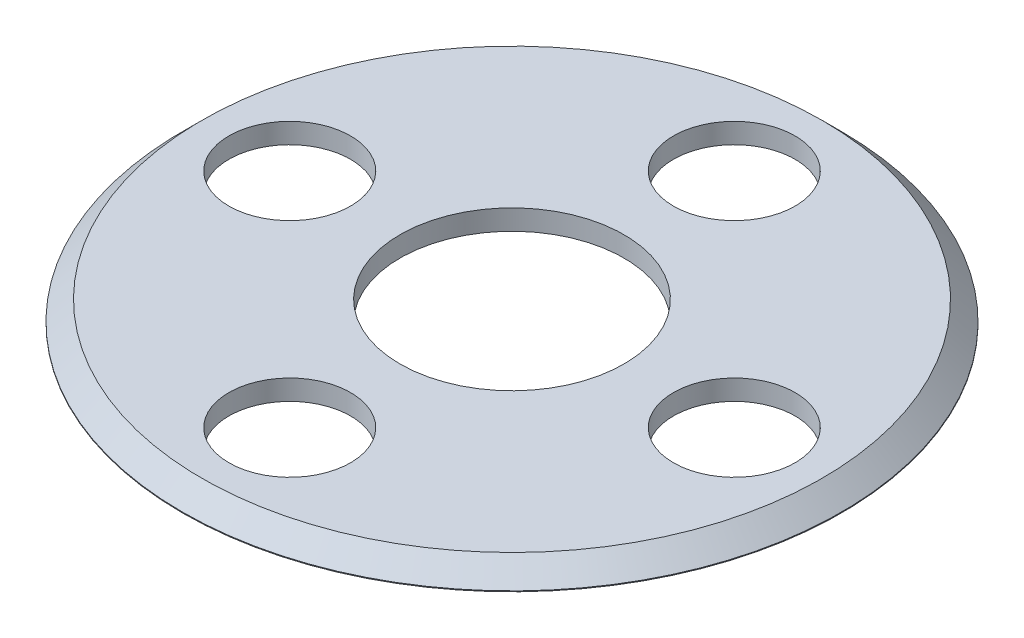
SolidWorks part; units mm, degrees
other "DetailItem2"
other "DetailItem3"
other "DetailItem4"
material "Alum Plate"
ref_plane "Front Plane" through (0, 0, 0) normal (0, 0, 1) x (1, 0, 0)
ref_plane "Top Plane" through (0, 0, 0) normal (0, 1, 0) x (1, 0, 0)
ref_plane "Right Plane" through (0, 0, 0) normal (1, 0, 0) x (0, 0, -1)
ref_axis "Centerline" through (0, 10.4775, 0) along (0, -1, 0)
sketch "Sketch1" plane through (0, 0, 0) normal (0, 1, 0) x (1, 0, 0)
  circle A0 centre (0, 0) radius 23.9697
  dimension "OuterDiameter" = 47.9394
extrude "ToothOD" add sketch "Sketch1" along normal mid plane 4.7625
sketch "Sketch2" plane through (0, 2.3813, 0) normal (0, 1, 0) x (1, 0, 0)
  line L0 (0, 22.8013) -> (50000, 22.8013) construction
  line L1 (0, 23.9697) -> (50000, 23.9697) construction
  line L2 (0, 0) -> (0, 50000) construction
  arc A0 (-0.937, 23.5198) -> (0, 22.8013) centre (0, 23.7716) ccw
  arc A1 (-1.1386, 23.9426) -> (1.1386, 23.9426) centre (0, 0) cw
  circle A2 centre (0, 0) radius 23.9697 construction
  arc A3 (-0.937, 23.5198) -> (-1.0078, 23.7716) centre (-11.9754, 20.5533) ccw
  arc A4 (-1.0078, 23.7716) -> (-1.1386, 23.9426) centre (-1.2954, 23.6872) ccw
  circle A5 centre (0, 0) radius 23.9697 construction
  arc A6 (0.937, 23.5198) -> (1.0078, 23.7716) centre (11.9754, 20.5533) cw
  arc A7 (1.0078, 23.7716) -> (1.1386, 23.9426) centre (1.2954, 23.6872) cw
  arc A8 (0, 22.8013) -> (0.937, 23.5198) centre (0, 23.7716) ccw
  dimension "D1" = 1.9406
  dimension "D3" = 22.86
  dimension "D4" = 0.5994
  dimension "D2" = 1.1684
  dimension "D5" = 1.2954
extrude "ToothProfile" cut sketch "Sketch2" against normal through all
pattern_circular "ToothPattern" count 51 over 360 about axis through (0, 2.3813, 0) along (0, -1, 0) of "ToothProfile"
sketch "Sketch4" plane through (0, 0, 0) normal (0, 0, 1) x (1, 0, 0)
  line L0 (0, -5.08) -> (24.2237, -5.08)
  line L1 (0, -6.35) -> (25.7477, -6.35)
  line L2 (0, -6.35) -> (0, -5.08)
  line L3 (25.7477, -6.35) -> (25.7477, -5.842)
  line L4 (0, 0) -> (50000, 0) construction
  line L5 (25.7477, 6.35) -> (25.7477, 5.842)
  line L6 (0, 6.35) -> (0, 5.08)
  line L7 (0, 6.35) -> (25.7477, 6.35)
  line L8 (0, 5.08) -> (24.2237, 5.08)
  arc A0 (24.2237, -5.08) -> (24.6788, -5.1726) centre (23.944, -7.618) cw
  arc A2 (24.6788, -5.1726) -> (25.7477, -5.842) centre (23.5462, -8.1694) cw
  arc A3 (24.6788, 5.1726) -> (25.7477, 5.842) centre (23.5462, 8.1694) ccw
  arc A4 (24.2237, 5.08) -> (24.6788, 5.1726) centre (23.944, 7.618) ccw
  dimension "FlangeID" = 24.2237
  dimension "FlangeOD" = 25.7477
  dimension "D1" = 1.27
  dimension "D2" = 0.508
  dimension "D3" = 5.08
  dimension "D4" = 12.7
sketch "Sketch7" plane through (0, 0, 0) normal (0, -1, 0) x (1, 0, 0)
  line L1 (3.6662, 6.35) -> (-3.6662, 6.35)
  line L2 (-3.6662, 6.35) -> (-7.3323, 0)
  line L3 (-7.3323, 0) -> (-3.6662, -6.35)
  line L4 (-3.6662, -6.35) -> (3.6662, -6.35)
  line L5 (3.6662, -6.35) -> (7.3323, 0)
  line L6 (7.3323, 0) -> (3.6662, 6.35)
  circle A0 centre (0, 0) radius 6.35 construction
  dimension "HexBoreDi," = 12.7
extrude "Bore" [suppressed] cut sketch "Sketch7" against normal through all both and the other way through all
sketch "Sketch13" plane through (0, 2.3813, 0) normal (0, 1, 0) x (1, 0, 0)
  line L0 (-3.81, 20.2565) -> (3.81, 20.2565) construction
  line L4 (0, 20.2565) -> (0, 17.399) construction
  arc A0 (-3.81, 20.2565) -> (3.81, 20.2565) centre (0, 17.399) ccw
  circle A1 centre (0, 0) radius 8.7694
  arc A2 (3.81, 20.2565) -> (-3.81, 20.2565) centre (0, 17.399) ccw
  dimension "D1" = 9.525
  dimension "D3" = 17.5387
  dimension "D2" = 17.399
  dimension "D4" = 7.62
extrude "Cut-Extrude2" cut sketch "Sketch13" against normal through all
pattern_circular "CirPattern1" count 4 over 360 about axis through (0, -2.3813, 0) along (0, 1, 0) of "Cut-Extrude2"
sketch "Sketch14" plane through (0, 2.3813, 0) normal (0, 1, 0) x (1, 0, 0)
  circle A0 centre (0, 0) radius 22.733
  circle A1 centre (0, 0) radius 23.9697
  arc A3 (-3.2802, -23.7442) -> (-2.6104, -23.8271) centre (0, 0) ccw construction
  dimension "D1" = 45.466
extrude "Cut-Extrude3" [suppressed] cut sketch "Sketch14" against normal through all
sketch "Sketch15" plane through (0, 2.3813, 0) normal (0, 1, 0) x (1, 0, 0)
  circle A0 centre (0, 0) radius 25.7969
  arc A306 (6.9442, 22.9418) -> (6.7756, 22.8078) centre (7.0339, 22.6558) ccw
  arc A307 (6.7756, 22.8078) -> (6.6455, 22.5808) centre (16.6269, 17.0116) ccw
  arc A308 (4.8281, 23.038) -> (6.6455, 22.5808) centre (5.7982, 23.0536) ccw
  arc A309 (4.8281, 23.038) -> (4.8208, 23.2994) centre (-6.6004, 22.8535) ccw
  arc A310 (4.8208, 23.2994) -> (4.7357, 23.4972) centre (4.5214, 23.2877) ccw
  arc A311 (4.7357, 23.4972) -> (4.0723, 23.6213) centre (0, 0) ccw
  arc A312 (4.0723, 23.6213) -> (3.9214, 23.4676) centre (4.1965, 23.3485) ccw
  arc A313 (3.9214, 23.4676) -> (3.8202, 23.2264) centre (14.4104, 18.9259) ccw
  arc A314 (1.9604, 23.4567) -> (3.8202, 23.2264) centre (2.9212, 23.5914) ccw
  arc A315 (1.9604, 23.4567) -> (1.9211, 23.7153) centre (-9.3589, 21.8692) ccw
  arc A316 (1.9211, 23.7153) -> (1.8123, 23.9011) centre (1.6253, 23.6668) ccw
  arc A317 (1.8123, 23.9011) -> (1.1386, 23.9426) centre (0, 0) ccw
  arc A318 (1.1386, 23.9426) -> (1.0078, 23.7716) centre (1.2954, 23.6872) ccw
  arc A319 (1.0078, 23.7716) -> (0.937, 23.5198) centre (11.9754, 20.5533) ccw
  arc A320 (-0.937, 23.5198) -> (0.937, 23.5198) centre (0, 23.7716) ccw
  arc A321 (-0.937, 23.5198) -> (-1.0078, 23.7716) centre (-11.9754, 20.5533) ccw
  arc A322 (-1.0078, 23.7716) -> (-1.1386, 23.9426) centre (-1.2954, 23.6872) ccw
  arc A323 (-1.1386, 23.9426) -> (-1.8123, 23.9011) centre (0, 0) ccw
  arc A324 (-1.8123, 23.9011) -> (-1.9211, 23.7153) centre (-1.6253, 23.6668) ccw
  arc A325 (-1.9211, 23.7153) -> (-1.9604, 23.4567) centre (9.3589, 21.8692) ccw
  arc A326 (-3.8202, 23.2264) -> (-1.9604, 23.4567) centre (-2.9212, 23.5914) ccw
  arc A327 (-3.8202, 23.2264) -> (-3.9214, 23.4676) centre (-14.4104, 18.9259) ccw
  arc A328 (-3.9214, 23.4676) -> (-4.0723, 23.6213) centre (-4.1965, 23.3485) ccw
  arc A329 (-4.0723, 23.6213) -> (-4.7357, 23.4972) centre (0, 0) ccw
  arc A330 (-4.7357, 23.4972) -> (-4.8208, 23.2994) centre (-4.5214, 23.2877) ccw
  arc A331 (-4.8208, 23.2994) -> (-4.8281, 23.038) centre (6.6004, 22.8535) ccw
  arc A332 (-6.6455, 22.5808) -> (-4.8281, 23.038) centre (-5.7982, 23.0536) ccw
  arc A333 (-6.6455, 22.5808) -> (-6.7756, 22.8078) centre (-16.6269, 17.0116) ccw
  arc A334 (-6.7756, 22.8078) -> (-6.9442, 22.9418) centre (-7.0339, 22.6558) ccw
  arc A335 (-6.9442, 22.9418) -> (-7.5873, 22.7372) centre (0, 0) ccw
  arc A336 (-7.5873, 22.7372) -> (-7.6475, 22.5304) centre (-7.3489, 22.5556) ccw
  arc A337 (-7.6475, 22.5304) -> (-7.6226, 22.27) centre (3.742, 23.4914) ccw
  arc A338 (-9.3701, 21.593) -> (-7.6226, 22.27) centre (-8.5873, 22.1663) ccw
  arc A339 (-9.3701, 21.593) -> (-9.527, 21.8023) centre (-18.5914, 14.8394) ccw
  arc A340 (-9.527, 21.8023) -> (-9.7108, 21.9145) centre (-9.7647, 21.6197) ccw
  arc A341 (-9.7108, 21.9145) -> (-10.324, 21.6324) centre (0, 0) ccw
  arc A342 (-10.324, 21.6324) -> (-10.3583, 21.4198) centre (-10.065, 21.4816) ccw
  arc A343 (-10.3583, 21.4198) -> (-10.3015, 21.1645) centre (0.8268, 23.7732) ccw
  arc A344 (-11.9526, 20.2779) -> (-10.3015, 21.1645) centre (-11.2462, 20.9431) ccw
  arc A345 (-11.9526, 20.2779) -> (-12.1341, 20.4663) centre (-20.2741, 12.4423) ccw
  arc A346 (-12.1341, 20.4663) -> (-12.3303, 20.5551) centre (-12.3475, 20.2559) ccw
  arc A347 (-12.3303, 20.5551) -> (-12.9041, 20.1998) centre (0, 0) ccw
  arc A348 (-12.9041, 20.1998) -> (-12.912, 19.9846) centre (-12.6285, 20.0819) ccw
  arc A349 (-12.912, 19.9846) -> (-12.8243, 19.7382) centre (-2.1009, 23.6946) ccw
  arc A350 (-14.3539, 18.6554) -> (-12.8243, 19.7382) centre (-13.7346, 19.4023) ccw
  arc A351 (-14.3539, 18.6554) -> (-14.5572, 18.82) centre (-21.6494, 9.8565) ccw
  arc A352 (-14.5572, 18.82) -> (-14.7628, 18.884) centre (-14.7431, 18.585) ccw
  arc A353 (-14.7628, 18.884) -> (-15.2886, 18.4609) centre (0, 0) ccw
  arc A354 (-15.2886, 18.4609) -> (-15.27, 18.2464) centre (-15.0006, 18.3778) ccw
  arc A355 (-15.27, 18.2464) -> (-15.1527, 18.0126) centre (-4.9968, 23.2569) ccw
  arc A356 (-16.5376, 16.75) -> (-15.1527, 18.0126) centre (-16.0148, 17.5674) ccw
  arc A357 (-16.5376, 16.75) -> (-16.7596, 16.8885) centre (-22.6966, 7.1213) ccw
  arc A358 (-16.7596, 16.8885) -> (-16.9715, 16.9267) centre (-16.9153, 16.6323) ccw
  arc A359 (-16.9715, 16.9267) -> (-17.4414, 16.4422) centre (0, 0) ccw
  arc A360 (-17.4414, 16.4422) -> (-17.3966, 16.2316) centre (-17.1454, 16.3951) ccw
  arc A361 (-17.3966, 16.2316) -> (-17.2514, 16.014) centre (-7.8169, 22.4665) ccw
  arc A362 (-18.4707, 14.5908) -> (-17.2514, 16.014) centre (-18.0523, 15.4662) ccw
  arc A363 (-18.4707, 14.5908) -> (-18.708, 14.7009) centre (-23.3997, 4.2782) ccw
  arc A364 (-18.708, 14.7009) -> (-18.923, 14.7128) centre (-18.831, 14.4276) ccw
  arc A365 (-18.923, 14.7128) -> (-19.3297, 14.1742) centre (0, 0) ccw
  arc A366 (-19.3297, 14.1742) -> (-19.2594, 13.9707) centre (-19.0302, 14.1638) ccw
  arc A367 (-19.2594, 13.9707) -> (-19.0886, 13.7726) centre (-10.5185, 21.3356) ccw
  arc A368 (-20.1237, 12.2104) -> (-19.0886, 13.7726) centre (-19.8161, 13.1306) ccw
  arc A369 (-20.1237, 12.2104) -> (-20.3727, 12.2905) centre (-23.7481, 1.3702) ccw
  arc A370 (-20.3727, 12.2905) -> (-20.5876, 12.2759) centre (-20.4612, 12.0041) ccw
  arc A371 (-20.5876, 12.2759) -> (-20.925, 11.6914) centre (0, 0) ccw
  arc A372 (-20.925, 11.6914) -> (-20.8302, 11.4981) centre (-20.6265, 11.7179) ccw
  arc A373 (-20.8302, 11.4981) -> (-20.6364, 11.3225) centre (-13.0607, 19.8813) ccw
  arc A374 (-21.4717, 9.6449) -> (-20.6364, 11.3225) centre (-21.2795, 10.5959) ccw
  arc A375 (-21.4717, 9.6449) -> (-21.7287, 9.6938) centre (-23.7365, -1.5585) ccw
  arc A376 (-21.7287, 9.6938) -> (-21.9401, 9.6529) centre (-21.7813, 9.3987) ccw
  arc A377 (-21.9401, 9.6529) -> (-22.2032, 9.0314) centre (0, 0) ccw
  arc A378 (-22.2032, 9.0314) -> (-22.0853, 8.8511) centre (-21.9102, 9.0943) ccw
  arc A379 (-22.0853, 8.8511) -> (-21.8713, 8.7007) centre (-15.4049, 18.1256) ccw
  arc A380 (-22.4942, 6.9331) -> (-21.8713, 8.7007) centre (-22.4203, 7.9006) ccw
  arc A381 (-22.4942, 6.9331) -> (-22.7552, 6.9501) centre (-23.365, -4.4636) ccw
  arc A382 (-22.7552, 6.9501) -> (-22.96, 6.8836) centre (-22.7712, 6.6508) ccw
  arc A383 (-22.96, 6.8836) -> (-23.1447, 6.2344) centre (0, 0) ccw
  arc A384 (-23.1447, 6.2344) -> (-23.0056, 6.07) centre (-22.8617, 6.3329) ccw
  arc A385 (-23.0056, 6.07) -> (-22.7748, 5.947) centre (-17.5156, 16.0952) ccw
  arc A386 (-23.1757, 4.1163) -> (-22.7748, 5.947) centre (-23.2212, 5.0855) ccw
  arc A387 (-23.1757, 4.1163) -> (-23.4368, 4.1011) centre (-22.6394, -7.3011) ccw
  arc A388 (-23.4368, 4.1011) -> (-23.6319, 4.0099) centre (-23.4159, 3.8021) ccw
  arc A389 (-23.6319, 4.0099) -> (-23.7355, 3.3429) centre (0, 0) ccw
  arc A390 (-23.7355, 3.3429) -> (-23.5772, 3.1969) centre (-23.4666, 3.4755) ccw
  arc A391 (-23.5772, 3.1969) -> (-23.333, 3.1032) centre (-19.3607, 13.8207) ccw
  arc A392 (-23.5059, 1.2371) -> (-23.333, 3.1032) centre (-23.6702, 2.1934) ccw
  arc A393 (-23.5059, 1.2371) -> (-23.7632, 1.1899) centre (-21.5706, -10.0279) ccw
  arc A394 (-23.7632, 1.1899) -> (-23.9456, 1.0754) centre (-23.7057, 0.8957) ccw
  arc A395 (-23.9456, 1.0754) -> (-23.9664, 0.4008) centre (0, 0) ccw
  arc A396 (-23.9664, 0.4008) -> (-23.7913, 0.2753) centre (-23.7159, 0.5653) ccw
  arc A397 (-23.7913, 0.2753) -> (-23.5375, 0.2123) centre (-20.9124, 11.3368) ccw
  arc A398 (-23.4798, -1.6609) -> (-23.5375, 0.2123) centre (-23.7603, -0.732) ccw
  arc A399 (-23.4798, -1.6609) -> (-23.7293, -1.7394) centre (-20.1748, -12.6026) ccw
  arc A400 (-23.7293, -1.7394) -> (-23.8962, -1.8754) centre (-23.6361, -2.0242) ccw
  arc A401 (-23.8962, -1.8754) -> (-23.834, -2.5474) centre (0, 0) ccw
  arc A402 (-23.834, -2.5474) -> (-23.6449, -2.6505) centre (-23.6056, -2.3533) ccw
  arc A403 (-23.6449, -2.6505) -> (-23.3852, -2.6818) centre (-22.147, 8.6809) ccw
  arc A404 (-23.0977, -4.5337) -> (-23.3852, -2.6818) centre (-23.4903, -3.6464) ccw
  arc A405 (-23.0977, -4.5337) -> (-23.3357, -4.6422) centre (-18.4732, -14.9864) ccw
  arc A406 (-23.3357, -4.6422) -> (-23.4846, -4.7978) centre (-23.2082, -4.9135) ccw
  arc A407 (-23.4846, -4.7978) -> (-23.3403, -5.4571) centre (0, 0) ccw
  arc A408 (-23.3403, -5.4571) -> (-23.1399, -5.5361) centre (-23.1375, -5.2364) ccw
  arc A409 (-23.1399, -5.5361) -> (-22.8783, -5.5352) centre (-23.0459, 5.8935) ccw
  arc A410 (-22.3655, -7.3378) -> (-22.8783, -5.5352) centre (-22.8641, -6.5054) ccw
  arc A411 (-22.3655, -7.3378) -> (-22.5883, -7.4747) centre (-16.4915, -17.1429) ccw
  arc A412 (-22.5883, -7.4747) -> (-22.7171, -7.6474) centre (-22.4285, -7.7283) ccw
  arc A413 (-22.7171, -7.6474) -> (-22.4927, -8.2839) centre (0, 0) ccw
  arc A414 (-22.4927, -8.2839) -> (-22.2842, -8.3377) centre (-22.3186, -8.04) ccw
  arc A415 (-22.2842, -8.3377) -> (-22.0247, -8.3048) centre (-23.5955, 3.0168) ccw
  arc A416 (-21.2942, -10.0306) -> (-22.0247, -8.3048) centre (-21.8914, -9.2658) ccw
  arc A417 (-21.2942, -10.0306) -> (-21.4986, -10.1939) centre (-14.2598, -19.0396) ccw
  arc A418 (-21.4986, -10.1939) -> (-21.6051, -10.3811) centre (-21.3087, -10.4259) ccw
  arc A419 (-21.6051, -10.3811) -> (-21.3043, -10.9852) centre (0, 0) ccw
  arc A420 (-21.3043, -10.9852) -> (-21.0907, -11.013) centre (-21.1614, -10.7217) ccw
  arc A421 (-21.0907, -11.013) -> (-20.8372, -10.9484) centre (-23.7874, 0.0943) ccw
  arc A422 (-19.9002, -12.5714) -> (-20.8372, -10.9484) centre (-20.5868, -11.8858) ccw
  arc A423 (-19.9002, -12.5714) -> (-20.0829, -12.7586) centre (-11.812, -20.6476) ccw
  arc A424 (-20.0829, -12.7586) -> (-20.1656, -12.9574) centre (-19.866, -12.9654) ccw
  arc A425 (-20.1656, -12.9574) -> (-19.7928, -13.52) centre (0, 0) ccw
  arc A426 (-19.7928, -13.52) -> (-19.5775, -13.5213) centre (-19.6834, -13.241) ccw
  arc A427 (-19.5775, -13.5213) -> (-19.3339, -13.4261) centre (-23.6187, -2.8296) ccw
  arc A428 (-18.2045, -14.9216) -> (-19.3339, -13.4261) centre (-18.9701, -14.3256) ccw
  arc A429 (-18.2045, -14.9216) -> (-18.3628, -15.1298) centre (-9.1851, -21.9427) ccw
  arc A430 (-18.3628, -15.1298) -> (-18.4205, -15.3373) centre (-18.1221, -15.3085) ccw
  arc A431 (-18.4205, -15.3373) -> (-17.9814, -15.8499) centre (0, 0) ccw
  arc A432 (-17.9814, -15.8499) -> (-17.7675, -15.8247) centre (-17.9071, -15.5595) ccw
  arc A433 (-17.7675, -15.8247) -> (-17.5374, -15.7002) centre (-23.0919, -5.7106) ccw
  arc A434 (-16.2328, -17.0456) -> (-17.5374, -15.7002) centre (-17.0659, -16.5482) ccw
  arc A435 (-16.2328, -17.0456) -> (-16.3643, -17.2717) centre (-6.419, -22.9051) ccw
  arc A436 (-16.3643, -17.2717) -> (-16.3961, -17.4847) centre (-16.1035, -17.4194) ccw
  arc A437 (-16.3961, -17.4847) -> (-15.8973, -17.9394) centre (0, 0) ccw
  arc A438 (-15.8973, -17.9394) -> (-15.6881, -17.8882) centre (-15.8593, -17.6421) ccw
  arc A439 (-15.6881, -17.8882) -> (-15.4751, -17.7363) centre (-22.2152, -8.505) ccw
  arc A440 (-14.0151, -18.9112) -> (-15.4751, -17.7363) centre (-14.903, -18.52) ccw
  arc A441 (-14.0151, -18.9112) -> (-14.1178, -19.1518) centre (-3.5556, -23.5203) ccw
  arc A442 (-14.1178, -19.1518) -> (-14.1231, -19.3671) centre (-13.8408, -19.2664) ccw
  arc A443 (-14.1231, -19.3671) -> (-13.5723, -19.757) centre (0, 0) ccw
  arc A444 (-13.5723, -19.757) -> (-13.371, -19.6805) centre (-13.5711, -19.4573) ccw
  arc A445 (-13.371, -19.6805) -> (-13.1782, -19.5036) centre (-21.0016, -11.1706) ccw
  arc A446 (-11.5849, -20.4902) -> (-13.1782, -19.5036) centre (-12.5141, -20.211) ccw
  arc A447 (-11.5849, -20.4902) -> (-11.6573, -20.7416) centre (-0.6383, -23.779) ccw
  arc A448 (-11.6573, -20.7416) -> (-11.6361, -20.9559) centre (-11.3683, -20.8212) ccw
  arc A449 (-11.6361, -20.9559) -> (-11.0415, -21.2752) centre (0, 0) ccw
  arc A450 (-11.0415, -21.2752) -> (-10.8511, -21.1744) centre (-11.0771, -20.9776) ccw
  arc A451 (-10.8511, -21.1744) -> (-10.6816, -20.9753) centre (-19.4697, -13.6667) ccw
  arc A452 (-8.9791, -21.7585) -> (-10.6816, -20.9753) centre (-9.9356, -21.5957) ccw
  arc A453 (-8.9791, -21.7585) -> (-9.02, -22.0169) centre (2.2887, -23.6772) ccw
  arc A454 (-9.02, -22.0169) -> (-8.9727, -22.227) centre (-8.7235, -22.0604) ccw
  arc A455 (-8.9727, -22.227) -> (-8.3433, -22.4708) centre (0, 0) ccw
  arc A456 (-8.3433, -22.4708) -> (-8.1668, -22.3474) centre (-8.4153, -22.1798) ccw
  arc A457 (-8.1668, -22.3474) -> (-8.023, -22.1289) centre (-17.6426, -15.9558) ccw
  arc A458 (-6.2371, -22.697) -> (-8.023, -22.1289) centre (-7.2064, -22.6529) ccw
  arc A459 (-6.2371, -22.697) -> (-6.246, -22.9585) centre (5.181, -23.2165) ccw
  arc A460 (-6.246, -22.9585) -> (-6.1732, -23.1611) centre (-5.9464, -22.9652) ccw
  arc A461 (-6.1732, -23.1611) -> (-5.5187, -23.3258) centre (0, 0) ccw
  arc A462 (-5.5187, -23.3258) -> (-5.3587, -23.1816) centre (-5.6259, -23.0458) ccw
  arc A463 (-5.3587, -23.1816) -> (-5.2428, -22.9471) centre (-15.5481, -18.0029) ccw
  arc A464 (-3.4007, -23.2915) -> (-5.2428, -22.9471) centre (-4.368, -23.3668) ccw
  arc A465 (-3.4007, -23.2915) -> (-3.3774, -23.552) centre (7.9948, -22.4038) ccw
  arc A466 (-3.3774, -23.552) -> (-3.2802, -23.7442) centre (-3.0792, -23.5219) ccw
  arc A467 (-3.2802, -23.7442) -> (-2.6104, -23.8271) centre (0, 0) ccw
  arc A468 (-2.6104, -23.8271) -> (-2.4693, -23.6645) centre (-2.7511, -23.5625) ccw
  arc A469 (-2.4693, -23.6645) -> (-2.3832, -23.4175) centre (-13.2179, -19.7771) ccw
  arc A470 (-0.5126, -23.5328) -> (-2.3832, -23.4175) centre (-1.4634, -23.7265) ccw
  arc A471 (-0.5126, -23.5328) -> (-0.4575, -23.7885) centre (10.6874, -21.2516) ccw
  arc A472 (-0.4575, -23.7885) -> (-0.3375, -23.9673) centre (-0.1653, -23.722) ccw
  arc A473 (-0.3375, -23.9673) -> (0.3375, -23.9673) centre (0, 0) ccw
  arc A474 (0.3375, -23.9673) -> (0.4575, -23.7885) centre (0.1653, -23.722) ccw
  arc A475 (0.4575, -23.7885) -> (0.5126, -23.5328) centre (-10.6874, -21.2516) ccw
  arc A476 (2.3832, -23.4175) -> (0.5126, -23.5328) centre (1.4634, -23.7265) ccw
  arc A477 (2.3832, -23.4175) -> (2.4693, -23.6645) centre (13.2179, -19.7771) ccw
  arc A478 (2.4693, -23.6645) -> (2.6104, -23.8271) centre (2.7511, -23.5625) ccw
  arc A479 (2.6104, -23.8271) -> (3.2802, -23.7442) centre (0, 0) ccw
  arc A480 (3.2802, -23.7442) -> (3.3774, -23.552) centre (3.0792, -23.5219) ccw
  arc A481 (3.3774, -23.552) -> (3.4007, -23.2915) centre (-7.9948, -22.4038) ccw
  arc A482 (5.2428, -22.9471) -> (3.4007, -23.2915) centre (4.368, -23.3668) ccw
  arc A483 (5.2428, -22.9471) -> (5.3587, -23.1816) centre (15.5481, -18.0029) ccw
  arc A484 (5.3587, -23.1816) -> (5.5187, -23.3258) centre (5.6259, -23.0458) ccw
  arc A485 (5.5187, -23.3258) -> (6.1732, -23.1611) centre (0, 0) ccw
  arc A486 (6.1732, -23.1611) -> (6.246, -22.9585) centre (5.9464, -22.9652) ccw
  arc A487 (6.246, -22.9585) -> (6.2371, -22.697) centre (-5.181, -23.2165) ccw
  arc A488 (8.023, -22.1289) -> (6.2371, -22.697) centre (7.2064, -22.6529) ccw
  arc A489 (8.023, -22.1289) -> (8.1668, -22.3474) centre (17.6426, -15.9558) ccw
  arc A490 (8.1668, -22.3474) -> (8.3433, -22.4708) centre (8.4153, -22.1798) ccw
  arc A491 (8.3433, -22.4708) -> (8.9727, -22.227) centre (0, 0) ccw
  arc A492 (8.9727, -22.227) -> (9.02, -22.0169) centre (8.7235, -22.0604) ccw
  arc A493 (9.02, -22.0169) -> (8.9791, -21.7585) centre (-2.2887, -23.6772) ccw
  arc A494 (10.6816, -20.9753) -> (8.9791, -21.7585) centre (9.9356, -21.5957) ccw
  arc A495 (10.6816, -20.9753) -> (10.8511, -21.1744) centre (19.4697, -13.6667) ccw
  arc A496 (10.8511, -21.1744) -> (11.0415, -21.2752) centre (11.0771, -20.9776) ccw
  arc A497 (11.0415, -21.2752) -> (11.6361, -20.9559) centre (0, 0) ccw
  arc A498 (11.6361, -20.9559) -> (11.6573, -20.7416) centre (11.3683, -20.8212) ccw
  arc A499 (11.6573, -20.7416) -> (11.5849, -20.4902) centre (0.6383, -23.779) ccw
  arc A500 (13.1782, -19.5036) -> (11.5849, -20.4902) centre (12.5141, -20.211) ccw
  arc A501 (13.1782, -19.5036) -> (13.371, -19.6805) centre (21.0016, -11.1706) ccw
  arc A502 (13.371, -19.6805) -> (13.5723, -19.757) centre (13.5711, -19.4573) ccw
  arc A503 (13.5723, -19.757) -> (14.1231, -19.3671) centre (0, 0) ccw
  arc A504 (14.1231, -19.3671) -> (14.1178, -19.1518) centre (13.8408, -19.2664) ccw
  arc A505 (14.1178, -19.1518) -> (14.0151, -18.9112) centre (3.5556, -23.5203) ccw
  arc A506 (15.4751, -17.7363) -> (14.0151, -18.9112) centre (14.903, -18.52) ccw
  arc A507 (15.4751, -17.7363) -> (15.6881, -17.8882) centre (22.2152, -8.505) ccw
  arc A508 (15.6881, -17.8882) -> (15.8973, -17.9394) centre (15.8593, -17.6421) ccw
  arc A509 (15.8973, -17.9394) -> (16.3961, -17.4847) centre (0, 0) ccw
  arc A510 (16.3961, -17.4847) -> (16.3643, -17.2717) centre (16.1035, -17.4194) ccw
  arc A511 (16.3643, -17.2717) -> (16.2328, -17.0456) centre (6.419, -22.9051) ccw
  arc A512 (17.5374, -15.7002) -> (16.2328, -17.0456) centre (17.0659, -16.5482) ccw
  arc A513 (17.5374, -15.7002) -> (17.7675, -15.8247) centre (23.0919, -5.7106) ccw
  arc A514 (17.7675, -15.8247) -> (17.9814, -15.8499) centre (17.9071, -15.5595) ccw
  arc A515 (17.9814, -15.8499) -> (18.4205, -15.3373) centre (0, 0) ccw
  arc A516 (18.4205, -15.3373) -> (18.3628, -15.1298) centre (18.1221, -15.3085) ccw
  arc A517 (18.3628, -15.1298) -> (18.2045, -14.9216) centre (9.1851, -21.9427) ccw
  arc A518 (19.3339, -13.4261) -> (18.2045, -14.9216) centre (18.9701, -14.3256) ccw
  arc A519 (19.3339, -13.4261) -> (19.5775, -13.5213) centre (23.6187, -2.8296) ccw
  arc A520 (19.5775, -13.5213) -> (19.7928, -13.52) centre (19.6834, -13.241) ccw
  arc A521 (19.7928, -13.52) -> (20.1656, -12.9574) centre (0, 0) ccw
  arc A522 (20.1656, -12.9574) -> (20.0829, -12.7586) centre (19.866, -12.9654) ccw
  arc A523 (20.0829, -12.7586) -> (19.9002, -12.5714) centre (11.812, -20.6476) ccw
  arc A524 (20.8372, -10.9484) -> (19.9002, -12.5714) centre (20.5868, -11.8858) ccw
  arc A525 (20.8372, -10.9484) -> (21.0907, -11.013) centre (23.7874, 0.0943) ccw
  arc A526 (21.0907, -11.013) -> (21.3043, -10.9852) centre (21.1614, -10.7217) ccw
  arc A527 (21.3043, -10.9852) -> (21.6051, -10.3811) centre (0, 0) ccw
  arc A528 (21.6051, -10.3811) -> (21.4986, -10.1939) centre (21.3087, -10.4259) ccw
  arc A529 (21.4986, -10.1939) -> (21.2942, -10.0306) centre (14.2598, -19.0396) ccw
  arc A530 (22.0247, -8.3048) -> (21.2942, -10.0306) centre (21.8914, -9.2658) ccw
  arc A531 (22.0247, -8.3048) -> (22.2842, -8.3377) centre (23.5955, 3.0168) ccw
  arc A532 (22.2842, -8.3377) -> (22.4927, -8.2839) centre (22.3186, -8.04) ccw
  arc A533 (22.4927, -8.2839) -> (22.7171, -7.6474) centre (0, 0) ccw
  arc A534 (22.7171, -7.6474) -> (22.5883, -7.4747) centre (22.4285, -7.7283) ccw
  arc A535 (22.5883, -7.4747) -> (22.3655, -7.3378) centre (16.4915, -17.1429) ccw
  arc A536 (22.8783, -5.5352) -> (22.3655, -7.3378) centre (22.8641, -6.5054) ccw
  arc A537 (22.8783, -5.5352) -> (23.1399, -5.5361) centre (23.0459, 5.8935) ccw
  arc A538 (23.1399, -5.5361) -> (23.3403, -5.4571) centre (23.1375, -5.2364) ccw
  arc A539 (23.3403, -5.4571) -> (23.4846, -4.7978) centre (0, 0) ccw
  arc A540 (23.4846, -4.7978) -> (23.3357, -4.6422) centre (23.2082, -4.9135) ccw
  arc A541 (23.3357, -4.6422) -> (23.0977, -4.5337) centre (18.4732, -14.9864) ccw
  arc A542 (23.3852, -2.6818) -> (23.0977, -4.5337) centre (23.4903, -3.6464) ccw
  arc A543 (23.3852, -2.6818) -> (23.6449, -2.6505) centre (22.147, 8.6809) ccw
  arc A544 (23.6449, -2.6505) -> (23.834, -2.5474) centre (23.6056, -2.3533) ccw
  arc A545 (23.834, -2.5474) -> (23.8962, -1.8754) centre (0, 0) ccw
  arc A546 (23.8962, -1.8754) -> (23.7293, -1.7394) centre (23.6361, -2.0242) ccw
  arc A547 (23.7293, -1.7394) -> (23.4798, -1.6609) centre (20.1748, -12.6026) ccw
  arc A548 (23.5375, 0.2123) -> (23.4798, -1.6609) centre (23.7603, -0.732) ccw
  arc A549 (23.5375, 0.2123) -> (23.7913, 0.2753) centre (20.9124, 11.3368) ccw
  arc A550 (23.7913, 0.2753) -> (23.9664, 0.4008) centre (23.7159, 0.5653) ccw
  arc A551 (23.9664, 0.4008) -> (23.9456, 1.0754) centre (0, 0) ccw
  arc A552 (23.9456, 1.0754) -> (23.7632, 1.1899) centre (23.7057, 0.8957) ccw
  arc A553 (23.7632, 1.1899) -> (23.5059, 1.2371) centre (21.5706, -10.0279) ccw
  arc A554 (23.333, 3.1032) -> (23.5059, 1.2371) centre (23.6702, 2.1934) ccw
  arc A555 (23.333, 3.1032) -> (23.5772, 3.1969) centre (19.3607, 13.8207) ccw
  arc A556 (23.5772, 3.1969) -> (23.7355, 3.3429) centre (23.4666, 3.4755) ccw
  arc A557 (23.7355, 3.3429) -> (23.6319, 4.0099) centre (0, 0) ccw
  arc A558 (23.6319, 4.0099) -> (23.4368, 4.1011) centre (23.4159, 3.8021) ccw
  arc A559 (23.4368, 4.1011) -> (23.1757, 4.1163) centre (22.6394, -7.3011) ccw
  arc A560 (22.7748, 5.947) -> (23.1757, 4.1163) centre (23.2212, 5.0855) ccw
  arc A561 (22.7748, 5.947) -> (23.0056, 6.07) centre (17.5156, 16.0952) ccw
  arc A562 (23.0056, 6.07) -> (23.1447, 6.2344) centre (22.8617, 6.3329) ccw
  arc A563 (23.1447, 6.2344) -> (22.96, 6.8836) centre (0, 0) ccw
  arc A564 (22.96, 6.8836) -> (22.7552, 6.9501) centre (22.7712, 6.6508) ccw
  arc A565 (22.7552, 6.9501) -> (22.4942, 6.9331) centre (23.365, -4.4636) ccw
  arc A566 (21.8713, 8.7007) -> (22.4942, 6.9331) centre (22.4203, 7.9006) ccw
  arc A567 (21.8713, 8.7007) -> (22.0853, 8.8511) centre (15.4049, 18.1256) ccw
  arc A568 (22.0853, 8.8511) -> (22.2032, 9.0314) centre (21.9102, 9.0943) ccw
  arc A569 (22.2032, 9.0314) -> (21.9401, 9.6529) centre (0, 0) ccw
  arc A570 (21.9401, 9.6529) -> (21.7287, 9.6938) centre (21.7813, 9.3987) ccw
  arc A571 (21.7287, 9.6938) -> (21.4717, 9.6449) centre (23.7365, -1.5585) ccw
  arc A572 (20.6364, 11.3225) -> (21.4717, 9.6449) centre (21.2795, 10.5959) ccw
  arc A573 (20.6364, 11.3225) -> (20.8302, 11.4981) centre (13.0607, 19.8813) ccw
  arc A574 (20.8302, 11.4981) -> (20.925, 11.6914) centre (20.6265, 11.7179) ccw
  arc A575 (20.925, 11.6914) -> (20.5876, 12.2759) centre (0, 0) ccw
  arc A576 (20.5876, 12.2759) -> (20.3727, 12.2905) centre (20.4612, 12.0041) ccw
  arc A577 (20.3727, 12.2905) -> (20.1237, 12.2104) centre (23.7481, 1.3702) ccw
  arc A578 (19.0886, 13.7726) -> (20.1237, 12.2104) centre (19.8161, 13.1306) ccw
  arc A579 (19.0886, 13.7726) -> (19.2594, 13.9707) centre (10.5185, 21.3356) ccw
  arc A580 (19.2594, 13.9707) -> (19.3297, 14.1742) centre (19.0302, 14.1638) ccw
  arc A581 (19.3297, 14.1742) -> (18.923, 14.7128) centre (0, 0) ccw
  arc A582 (18.923, 14.7128) -> (18.708, 14.7009) centre (18.831, 14.4276) ccw
  arc A583 (18.708, 14.7009) -> (18.4707, 14.5908) centre (23.3997, 4.2782) ccw
  arc A584 (17.2514, 16.014) -> (18.4707, 14.5908) centre (18.0523, 15.4662) ccw
  arc A585 (17.2514, 16.014) -> (17.3966, 16.2316) centre (7.8169, 22.4665) ccw
  arc A586 (17.3966, 16.2316) -> (17.4414, 16.4422) centre (17.1454, 16.3951) ccw
  arc A587 (17.4414, 16.4422) -> (16.9715, 16.9267) centre (0, 0) ccw
  arc A588 (16.9715, 16.9267) -> (16.7596, 16.8885) centre (16.9153, 16.6323) ccw
  arc A589 (16.7596, 16.8885) -> (16.5376, 16.75) centre (22.6966, 7.1213) ccw
  arc A590 (15.1527, 18.0126) -> (16.5376, 16.75) centre (16.0148, 17.5674) ccw
  arc A591 (15.1527, 18.0126) -> (15.27, 18.2464) centre (4.9968, 23.2569) ccw
  arc A592 (15.27, 18.2464) -> (15.2886, 18.4609) centre (15.0006, 18.3778) ccw
  arc A593 (15.2886, 18.4609) -> (14.7628, 18.884) centre (0, 0) ccw
  arc A594 (14.7628, 18.884) -> (14.5572, 18.82) centre (14.7431, 18.585) ccw
  arc A595 (14.5572, 18.82) -> (14.3539, 18.6554) centre (21.6494, 9.8565) ccw
  arc A596 (12.8243, 19.7382) -> (14.3539, 18.6554) centre (13.7346, 19.4023) ccw
  arc A597 (12.8243, 19.7382) -> (12.912, 19.9846) centre (2.1009, 23.6946) ccw
  arc A598 (12.912, 19.9846) -> (12.9041, 20.1998) centre (12.6285, 20.0819) ccw
  arc A599 (12.9041, 20.1998) -> (12.3303, 20.5551) centre (0, 0) ccw
  arc A600 (12.3303, 20.5551) -> (12.1341, 20.4663) centre (12.3475, 20.2559) ccw
  arc A601 (12.1341, 20.4663) -> (11.9526, 20.2779) centre (20.2741, 12.4423) ccw
  arc A602 (10.3015, 21.1645) -> (11.9526, 20.2779) centre (11.2462, 20.9431) ccw
  arc A603 (10.3015, 21.1645) -> (10.3583, 21.4198) centre (-0.8268, 23.7732) ccw
  arc A604 (10.3583, 21.4198) -> (10.324, 21.6324) centre (10.065, 21.4816) ccw
  arc A605 (10.324, 21.6324) -> (9.7108, 21.9145) centre (0, 0) ccw
  arc A606 (9.7108, 21.9145) -> (9.527, 21.8023) centre (9.7647, 21.6197) ccw
  arc A607 (9.527, 21.8023) -> (9.3701, 21.593) centre (18.5914, 14.8394) ccw
  arc A608 (7.6226, 22.27) -> (9.3701, 21.593) centre (8.5873, 22.1663) ccw
  arc A609 (7.6226, 22.27) -> (7.6475, 22.5304) centre (-3.742, 23.4914) ccw
  arc A610 (7.6475, 22.5304) -> (7.5873, 22.7372) centre (7.3489, 22.5556) ccw
  arc A611 (7.5873, 22.7372) -> (6.9442, 22.9418) centre (0, 0) ccw
  arc A612 (6.9442, 22.9418) -> (6.7756, 22.8078) centre (7.0339, 22.6558) ccw
  arc A613 (6.7756, 22.8078) -> (6.6455, 22.5808) centre (16.6269, 17.0116) ccw
  arc A614 (4.8281, 23.038) -> (6.6455, 22.5808) centre (5.7982, 23.0536) ccw
  arc A615 (4.8281, 23.038) -> (4.8208, 23.2994) centre (-6.6004, 22.8535) ccw
  arc A616 (4.8208, 23.2994) -> (4.7357, 23.4972) centre (4.5214, 23.2877) ccw
  arc A617 (4.7357, 23.4972) -> (4.0723, 23.6213) centre (0, 0) ccw
  arc A618 (4.0723, 23.6213) -> (3.9214, 23.4676) centre (4.1965, 23.3485) ccw
  arc A619 (3.9214, 23.4676) -> (3.8202, 23.2264) centre (14.4104, 18.9259) ccw
  arc A620 (1.9604, 23.4567) -> (3.8202, 23.2264) centre (2.9212, 23.5914) ccw
  arc A621 (1.9604, 23.4567) -> (1.9211, 23.7153) centre (-9.3589, 21.8692) ccw
  arc A622 (1.9211, 23.7153) -> (1.8123, 23.9011) centre (1.6253, 23.6668) ccw
  arc A623 (1.8123, 23.9011) -> (1.1386, 23.9426) centre (0, 0) ccw
  arc A624 (1.1386, 23.9426) -> (1.0078, 23.7716) centre (1.2954, 23.6872) ccw
  arc A625 (1.0078, 23.7716) -> (0.937, 23.5198) centre (11.9754, 20.5533) ccw
  arc A626 (-0.937, 23.5198) -> (0.937, 23.5198) centre (0, 23.7716) ccw
  arc A627 (-0.937, 23.5198) -> (-1.0078, 23.7716) centre (-11.9754, 20.5533) ccw
  arc A628 (-1.0078, 23.7716) -> (-1.1386, 23.9426) centre (-1.2954, 23.6872) ccw
  arc A629 (-1.1386, 23.9426) -> (-1.8123, 23.9011) centre (0, 0) ccw
  arc A630 (-1.8123, 23.9011) -> (-1.9211, 23.7153) centre (-1.6253, 23.6668) ccw
  arc A631 (-1.9211, 23.7153) -> (-1.9604, 23.4567) centre (9.3589, 21.8692) ccw
  arc A632 (-3.8202, 23.2264) -> (-1.9604, 23.4567) centre (-2.9212, 23.5914) ccw
  arc A633 (-3.8202, 23.2264) -> (-3.9214, 23.4676) centre (-14.4104, 18.9259) ccw
  arc A634 (-3.9214, 23.4676) -> (-4.0723, 23.6213) centre (-4.1965, 23.3485) ccw
  arc A635 (-4.0723, 23.6213) -> (-4.7357, 23.4972) centre (0, 0) ccw
  arc A636 (-4.7357, 23.4972) -> (-4.8208, 23.2994) centre (-4.5214, 23.2877) ccw
  arc A637 (-4.8208, 23.2994) -> (-4.8281, 23.038) centre (6.6004, 22.8535) ccw
  arc A638 (-6.6455, 22.5808) -> (-4.8281, 23.038) centre (-5.7982, 23.0536) ccw
  arc A639 (-6.6455, 22.5808) -> (-6.7756, 22.8078) centre (-16.6269, 17.0116) ccw
  arc A640 (-6.7756, 22.8078) -> (-6.9442, 22.9418) centre (-7.0339, 22.6558) ccw
  arc A641 (-6.9442, 22.9418) -> (-7.5873, 22.7372) centre (0, 0) ccw
  arc A642 (-7.5873, 22.7372) -> (-7.6475, 22.5304) centre (-7.3489, 22.5556) ccw
  arc A643 (-7.6475, 22.5304) -> (-7.6226, 22.27) centre (3.742, 23.4914) ccw
  arc A644 (-9.3701, 21.593) -> (-7.6226, 22.27) centre (-8.5873, 22.1663) ccw
  arc A645 (-9.3701, 21.593) -> (-9.527, 21.8023) centre (-18.5914, 14.8394) ccw
  arc A646 (-9.527, 21.8023) -> (-9.7108, 21.9145) centre (-9.7647, 21.6197) ccw
  arc A647 (-9.7108, 21.9145) -> (-10.324, 21.6324) centre (0, 0) ccw
  arc A648 (-10.324, 21.6324) -> (-10.3583, 21.4198) centre (-10.065, 21.4816) ccw
  arc A649 (-10.3583, 21.4198) -> (-10.3015, 21.1645) centre (0.8268, 23.7732) ccw
  arc A650 (-11.9526, 20.2779) -> (-10.3015, 21.1645) centre (-11.2462, 20.9431) ccw
  arc A651 (-11.9526, 20.2779) -> (-12.1341, 20.4663) centre (-20.2741, 12.4423) ccw
  arc A652 (-12.1341, 20.4663) -> (-12.3303, 20.5551) centre (-12.3475, 20.2559) ccw
  arc A653 (-12.3303, 20.5551) -> (-12.9041, 20.1998) centre (0, 0) ccw
  arc A654 (-12.9041, 20.1998) -> (-12.912, 19.9846) centre (-12.6285, 20.0819) ccw
  arc A655 (-12.912, 19.9846) -> (-12.8243, 19.7382) centre (-2.1009, 23.6946) ccw
  arc A656 (-14.3539, 18.6554) -> (-12.8243, 19.7382) centre (-13.7346, 19.4023) ccw
  arc A657 (-14.3539, 18.6554) -> (-14.5572, 18.82) centre (-21.6494, 9.8565) ccw
  arc A658 (-14.5572, 18.82) -> (-14.7628, 18.884) centre (-14.7431, 18.585) ccw
  arc A659 (-14.7628, 18.884) -> (-15.2886, 18.4609) centre (0, 0) ccw
  arc A660 (-15.2886, 18.4609) -> (-15.27, 18.2464) centre (-15.0006, 18.3778) ccw
  arc A661 (-15.27, 18.2464) -> (-15.1527, 18.0126) centre (-4.9968, 23.2569) ccw
  arc A662 (-16.5376, 16.75) -> (-15.1527, 18.0126) centre (-16.0148, 17.5674) ccw
  arc A663 (-16.5376, 16.75) -> (-16.7596, 16.8885) centre (-22.6966, 7.1213) ccw
  arc A664 (-16.7596, 16.8885) -> (-16.9715, 16.9267) centre (-16.9153, 16.6323) ccw
  arc A665 (-16.9715, 16.9267) -> (-17.4414, 16.4422) centre (0, 0) ccw
  arc A666 (-17.4414, 16.4422) -> (-17.3966, 16.2316) centre (-17.1454, 16.3951) ccw
  arc A667 (-17.3966, 16.2316) -> (-17.2514, 16.014) centre (-7.8169, 22.4665) ccw
  arc A668 (-18.4707, 14.5908) -> (-17.2514, 16.014) centre (-18.0523, 15.4662) ccw
  arc A669 (-18.4707, 14.5908) -> (-18.708, 14.7009) centre (-23.3997, 4.2782) ccw
  arc A670 (-18.708, 14.7009) -> (-18.923, 14.7128) centre (-18.831, 14.4276) ccw
  arc A671 (-18.923, 14.7128) -> (-19.3297, 14.1742) centre (0, 0) ccw
  arc A672 (-19.3297, 14.1742) -> (-19.2594, 13.9707) centre (-19.0302, 14.1638) ccw
  arc A673 (-19.2594, 13.9707) -> (-19.0886, 13.7726) centre (-10.5185, 21.3356) ccw
  arc A674 (-20.1237, 12.2104) -> (-19.0886, 13.7726) centre (-19.8161, 13.1306) ccw
  arc A675 (-20.1237, 12.2104) -> (-20.3727, 12.2905) centre (-23.7481, 1.3702) ccw
  arc A676 (-20.3727, 12.2905) -> (-20.5876, 12.2759) centre (-20.4612, 12.0041) ccw
  arc A677 (-20.5876, 12.2759) -> (-20.925, 11.6914) centre (0, 0) ccw
  arc A678 (-20.925, 11.6914) -> (-20.8302, 11.4981) centre (-20.6265, 11.7179) ccw
  arc A679 (-20.8302, 11.4981) -> (-20.6364, 11.3225) centre (-13.0607, 19.8813) ccw
  arc A680 (-21.4717, 9.6449) -> (-20.6364, 11.3225) centre (-21.2795, 10.5959) ccw
  arc A681 (-21.4717, 9.6449) -> (-21.7287, 9.6938) centre (-23.7365, -1.5585) ccw
  arc A682 (-21.7287, 9.6938) -> (-21.9401, 9.6529) centre (-21.7813, 9.3987) ccw
  arc A683 (-21.9401, 9.6529) -> (-22.2032, 9.0314) centre (0, 0) ccw
  arc A684 (-22.2032, 9.0314) -> (-22.0853, 8.8511) centre (-21.9102, 9.0943) ccw
  arc A685 (-22.0853, 8.8511) -> (-21.8713, 8.7007) centre (-15.4049, 18.1256) ccw
  arc A686 (-22.4942, 6.9331) -> (-21.8713, 8.7007) centre (-22.4203, 7.9006) ccw
  arc A687 (-22.4942, 6.9331) -> (-22.7552, 6.9501) centre (-23.365, -4.4636) ccw
  arc A688 (-22.7552, 6.9501) -> (-22.96, 6.8836) centre (-22.7712, 6.6508) ccw
  arc A689 (-22.96, 6.8836) -> (-23.1447, 6.2344) centre (0, 0) ccw
  arc A690 (-23.1447, 6.2344) -> (-23.0056, 6.07) centre (-22.8617, 6.3329) ccw
  arc A691 (-23.0056, 6.07) -> (-22.7748, 5.947) centre (-17.5156, 16.0952) ccw
  arc A692 (-23.1757, 4.1163) -> (-22.7748, 5.947) centre (-23.2212, 5.0855) ccw
  arc A693 (-23.1757, 4.1163) -> (-23.4368, 4.1011) centre (-22.6394, -7.3011) ccw
  arc A694 (-23.4368, 4.1011) -> (-23.6319, 4.0099) centre (-23.4159, 3.8021) ccw
  arc A695 (-23.6319, 4.0099) -> (-23.7355, 3.3429) centre (0, 0) ccw
  arc A696 (-23.7355, 3.3429) -> (-23.5772, 3.1969) centre (-23.4666, 3.4755) ccw
  arc A697 (-23.5772, 3.1969) -> (-23.333, 3.1032) centre (-19.3607, 13.8207) ccw
  arc A698 (-23.5059, 1.2371) -> (-23.333, 3.1032) centre (-23.6702, 2.1934) ccw
  arc A699 (-23.5059, 1.2371) -> (-23.7632, 1.1899) centre (-21.5706, -10.0279) ccw
  arc A700 (-23.7632, 1.1899) -> (-23.9456, 1.0754) centre (-23.7057, 0.8957) ccw
  arc A701 (-23.9456, 1.0754) -> (-23.9664, 0.4008) centre (0, 0) ccw
  arc A702 (-23.9664, 0.4008) -> (-23.7913, 0.2753) centre (-23.7159, 0.5653) ccw
  arc A703 (-23.7913, 0.2753) -> (-23.5375, 0.2123) centre (-20.9124, 11.3368) ccw
  arc A704 (-23.4798, -1.6609) -> (-23.5375, 0.2123) centre (-23.7603, -0.732) ccw
  arc A705 (-23.4798, -1.6609) -> (-23.7293, -1.7394) centre (-20.1748, -12.6026) ccw
  arc A706 (-23.7293, -1.7394) -> (-23.8962, -1.8754) centre (-23.6361, -2.0242) ccw
  arc A707 (-23.8962, -1.8754) -> (-23.834, -2.5474) centre (0, 0) ccw
  arc A708 (-23.834, -2.5474) -> (-23.6449, -2.6505) centre (-23.6056, -2.3533) ccw
  arc A709 (-23.6449, -2.6505) -> (-23.3852, -2.6818) centre (-22.147, 8.6809) ccw
  arc A710 (-23.0977, -4.5337) -> (-23.3852, -2.6818) centre (-23.4903, -3.6464) ccw
  arc A711 (-23.0977, -4.5337) -> (-23.3357, -4.6422) centre (-18.4732, -14.9864) ccw
  arc A712 (-23.3357, -4.6422) -> (-23.4846, -4.7978) centre (-23.2082, -4.9135) ccw
  arc A713 (-23.4846, -4.7978) -> (-23.3403, -5.4571) centre (0, 0) ccw
  arc A714 (-23.3403, -5.4571) -> (-23.1399, -5.5361) centre (-23.1375, -5.2364) ccw
  arc A715 (-23.1399, -5.5361) -> (-22.8783, -5.5352) centre (-23.0459, 5.8935) ccw
  arc A716 (-22.3655, -7.3378) -> (-22.8783, -5.5352) centre (-22.8641, -6.5054) ccw
  arc A717 (-22.3655, -7.3378) -> (-22.5883, -7.4747) centre (-16.4915, -17.1429) ccw
  arc A718 (-22.5883, -7.4747) -> (-22.7171, -7.6474) centre (-22.4285, -7.7283) ccw
  arc A719 (-22.7171, -7.6474) -> (-22.4927, -8.2839) centre (0, 0) ccw
  arc A720 (-22.4927, -8.2839) -> (-22.2842, -8.3377) centre (-22.3186, -8.04) ccw
  arc A721 (-22.2842, -8.3377) -> (-22.0247, -8.3048) centre (-23.5955, 3.0168) ccw
  arc A722 (-21.2942, -10.0306) -> (-22.0247, -8.3048) centre (-21.8914, -9.2658) ccw
  arc A723 (-21.2942, -10.0306) -> (-21.4986, -10.1939) centre (-14.2598, -19.0396) ccw
  arc A724 (-21.4986, -10.1939) -> (-21.6051, -10.3811) centre (-21.3087, -10.4259) ccw
  arc A725 (-21.6051, -10.3811) -> (-21.3043, -10.9852) centre (0, 0) ccw
  arc A726 (-21.3043, -10.9852) -> (-21.0907, -11.013) centre (-21.1614, -10.7217) ccw
  arc A727 (-21.0907, -11.013) -> (-20.8372, -10.9484) centre (-23.7874, 0.0943) ccw
  arc A728 (-19.9002, -12.5714) -> (-20.8372, -10.9484) centre (-20.5868, -11.8858) ccw
  arc A729 (-19.9002, -12.5714) -> (-20.0829, -12.7586) centre (-11.812, -20.6476) ccw
  arc A730 (-20.0829, -12.7586) -> (-20.1656, -12.9574) centre (-19.866, -12.9654) ccw
  arc A731 (-20.1656, -12.9574) -> (-19.7928, -13.52) centre (0, 0) ccw
  arc A732 (-19.7928, -13.52) -> (-19.5775, -13.5213) centre (-19.6834, -13.241) ccw
  arc A733 (-19.5775, -13.5213) -> (-19.3339, -13.4261) centre (-23.6187, -2.8296) ccw
  arc A734 (-18.2045, -14.9216) -> (-19.3339, -13.4261) centre (-18.9701, -14.3256) ccw
  arc A735 (-18.2045, -14.9216) -> (-18.3628, -15.1298) centre (-9.1851, -21.9427) ccw
  arc A736 (-18.3628, -15.1298) -> (-18.4205, -15.3373) centre (-18.1221, -15.3085) ccw
  arc A737 (-18.4205, -15.3373) -> (-17.9814, -15.8499) centre (0, 0) ccw
  arc A738 (-17.9814, -15.8499) -> (-17.7675, -15.8247) centre (-17.9071, -15.5595) ccw
  arc A739 (-17.7675, -15.8247) -> (-17.5374, -15.7002) centre (-23.0919, -5.7106) ccw
  arc A740 (-16.2328, -17.0456) -> (-17.5374, -15.7002) centre (-17.0659, -16.5482) ccw
  arc A741 (-16.2328, -17.0456) -> (-16.3643, -17.2717) centre (-6.419, -22.9051) ccw
  arc A742 (-16.3643, -17.2717) -> (-16.3961, -17.4847) centre (-16.1035, -17.4194) ccw
  arc A743 (-16.3961, -17.4847) -> (-15.8973, -17.9394) centre (0, 0) ccw
  arc A744 (-15.8973, -17.9394) -> (-15.6881, -17.8882) centre (-15.8593, -17.6421) ccw
  arc A745 (-15.6881, -17.8882) -> (-15.4751, -17.7363) centre (-22.2152, -8.505) ccw
  arc A746 (-14.0151, -18.9112) -> (-15.4751, -17.7363) centre (-14.903, -18.52) ccw
  arc A747 (-14.0151, -18.9112) -> (-14.1178, -19.1518) centre (-3.5556, -23.5203) ccw
  arc A748 (-14.1178, -19.1518) -> (-14.1231, -19.3671) centre (-13.8408, -19.2664) ccw
  arc A749 (-14.1231, -19.3671) -> (-13.5723, -19.757) centre (0, 0) ccw
  arc A750 (-13.5723, -19.757) -> (-13.371, -19.6805) centre (-13.5711, -19.4573) ccw
  arc A751 (-13.371, -19.6805) -> (-13.1782, -19.5036) centre (-21.0016, -11.1706) ccw
  arc A752 (-11.5849, -20.4902) -> (-13.1782, -19.5036) centre (-12.5141, -20.211) ccw
  arc A753 (-11.5849, -20.4902) -> (-11.6573, -20.7416) centre (-0.6383, -23.779) ccw
  arc A754 (-11.6573, -20.7416) -> (-11.6361, -20.9559) centre (-11.3683, -20.8212) ccw
  arc A755 (-11.6361, -20.9559) -> (-11.0415, -21.2752) centre (0, 0) ccw
  arc A756 (-11.0415, -21.2752) -> (-10.8511, -21.1744) centre (-11.0771, -20.9776) ccw
  arc A757 (-10.8511, -21.1744) -> (-10.6816, -20.9753) centre (-19.4697, -13.6667) ccw
  arc A758 (-8.9791, -21.7585) -> (-10.6816, -20.9753) centre (-9.9356, -21.5957) ccw
  arc A759 (-8.9791, -21.7585) -> (-9.02, -22.0169) centre (2.2887, -23.6772) ccw
  arc A760 (-9.02, -22.0169) -> (-8.9727, -22.227) centre (-8.7235, -22.0604) ccw
  arc A761 (-8.9727, -22.227) -> (-8.3433, -22.4708) centre (0, 0) ccw
  arc A762 (-8.3433, -22.4708) -> (-8.1668, -22.3474) centre (-8.4153, -22.1798) ccw
  arc A763 (-8.1668, -22.3474) -> (-8.023, -22.1289) centre (-17.6426, -15.9558) ccw
  arc A764 (-6.2371, -22.697) -> (-8.023, -22.1289) centre (-7.2064, -22.6529) ccw
  arc A765 (-6.2371, -22.697) -> (-6.246, -22.9585) centre (5.181, -23.2165) ccw
  arc A766 (-6.246, -22.9585) -> (-6.1732, -23.1611) centre (-5.9464, -22.9652) ccw
  arc A767 (-6.1732, -23.1611) -> (-5.5187, -23.3258) centre (0, 0) ccw
  arc A768 (-5.5187, -23.3258) -> (-5.3587, -23.1816) centre (-5.6259, -23.0458) ccw
  arc A769 (-5.3587, -23.1816) -> (-5.2428, -22.9471) centre (-15.5481, -18.0029) ccw
  arc A770 (-3.4007, -23.2915) -> (-5.2428, -22.9471) centre (-4.368, -23.3668) ccw
  arc A771 (-3.4007, -23.2915) -> (-3.3774, -23.552) centre (7.9948, -22.4038) ccw
  arc A772 (-3.3774, -23.552) -> (-3.2802, -23.7442) centre (-3.0792, -23.5219) ccw
  arc A773 (-3.2802, -23.7442) -> (-2.6104, -23.8271) centre (0, 0) ccw
  arc A774 (-2.6104, -23.8271) -> (-2.4693, -23.6645) centre (-2.7511, -23.5625) ccw
  arc A775 (-2.4693, -23.6645) -> (-2.3832, -23.4175) centre (-13.2179, -19.7771) ccw
  arc A776 (-0.5126, -23.5328) -> (-2.3832, -23.4175) centre (-1.4634, -23.7265) ccw
  arc A777 (-0.5126, -23.5328) -> (-0.4575, -23.7885) centre (10.6874, -21.2516) ccw
  arc A778 (-0.4575, -23.7885) -> (-0.3375, -23.9673) centre (-0.1653, -23.722) ccw
  arc A779 (-0.3375, -23.9673) -> (0.3375, -23.9673) centre (0, 0) ccw
  arc A780 (0.3375, -23.9673) -> (0.4575, -23.7885) centre (0.1653, -23.722) ccw
  arc A781 (0.4575, -23.7885) -> (0.5126, -23.5328) centre (-10.6874, -21.2516) ccw
  arc A782 (2.3832, -23.4175) -> (0.5126, -23.5328) centre (1.4634, -23.7265) ccw
  arc A783 (2.3832, -23.4175) -> (2.4693, -23.6645) centre (13.2179, -19.7771) ccw
  arc A784 (2.4693, -23.6645) -> (2.6104, -23.8271) centre (2.7511, -23.5625) ccw
  arc A785 (2.6104, -23.8271) -> (3.2802, -23.7442) centre (0, 0) ccw
  arc A786 (3.2802, -23.7442) -> (3.3774, -23.552) centre (3.0792, -23.5219) ccw
  arc A787 (3.3774, -23.552) -> (3.4007, -23.2915) centre (-7.9948, -22.4038) ccw
  arc A788 (5.2428, -22.9471) -> (3.4007, -23.2915) centre (4.368, -23.3668) ccw
  arc A789 (5.2428, -22.9471) -> (5.3587, -23.1816) centre (15.5481, -18.0029) ccw
  arc A790 (5.3587, -23.1816) -> (5.5187, -23.3258) centre (5.6259, -23.0458) ccw
  arc A791 (5.5187, -23.3258) -> (6.1732, -23.1611) centre (0, 0) ccw
  arc A792 (6.1732, -23.1611) -> (6.246, -22.9585) centre (5.9464, -22.9652) ccw
  arc A793 (6.246, -22.9585) -> (6.2371, -22.697) centre (-5.181, -23.2165) ccw
  arc A794 (8.023, -22.1289) -> (6.2371, -22.697) centre (7.2064, -22.6529) ccw
  arc A795 (8.023, -22.1289) -> (8.1668, -22.3474) centre (17.6426, -15.9558) ccw
  arc A796 (8.1668, -22.3474) -> (8.3433, -22.4708) centre (8.4153, -22.1798) ccw
  arc A797 (8.3433, -22.4708) -> (8.9727, -22.227) centre (0, 0) ccw
  arc A798 (8.9727, -22.227) -> (9.02, -22.0169) centre (8.7235, -22.0604) ccw
  arc A799 (9.02, -22.0169) -> (8.9791, -21.7585) centre (-2.2887, -23.6772) ccw
  arc A800 (10.6816, -20.9753) -> (8.9791, -21.7585) centre (9.9356, -21.5957) ccw
  arc A801 (10.6816, -20.9753) -> (10.8511, -21.1744) centre (19.4697, -13.6667) ccw
  arc A802 (10.8511, -21.1744) -> (11.0415, -21.2752) centre (11.0771, -20.9776) ccw
  arc A803 (11.0415, -21.2752) -> (11.6361, -20.9559) centre (0, 0) ccw
  arc A804 (11.6361, -20.9559) -> (11.6573, -20.7416) centre (11.3683, -20.8212) ccw
  arc A805 (11.6573, -20.7416) -> (11.5849, -20.4902) centre (0.6383, -23.779) ccw
  arc A806 (13.1782, -19.5036) -> (11.5849, -20.4902) centre (12.5141, -20.211) ccw
  arc A807 (13.1782, -19.5036) -> (13.371, -19.6805) centre (21.0016, -11.1706) ccw
  arc A808 (13.371, -19.6805) -> (13.5723, -19.757) centre (13.5711, -19.4573) ccw
  arc A809 (13.5723, -19.757) -> (14.1231, -19.3671) centre (0, 0) ccw
  arc A810 (14.1231, -19.3671) -> (14.1178, -19.1518) centre (13.8408, -19.2664) ccw
  arc A811 (14.1178, -19.1518) -> (14.0151, -18.9112) centre (3.5556, -23.5203) ccw
  arc A812 (15.4751, -17.7363) -> (14.0151, -18.9112) centre (14.903, -18.52) ccw
  arc A813 (15.4751, -17.7363) -> (15.6881, -17.8882) centre (22.2152, -8.505) ccw
  arc A814 (15.6881, -17.8882) -> (15.8973, -17.9394) centre (15.8593, -17.6421) ccw
  arc A815 (15.8973, -17.9394) -> (16.3961, -17.4847) centre (0, 0) ccw
  arc A816 (16.3961, -17.4847) -> (16.3643, -17.2717) centre (16.1035, -17.4194) ccw
  arc A817 (16.3643, -17.2717) -> (16.2328, -17.0456) centre (6.419, -22.9051) ccw
  arc A818 (17.5374, -15.7002) -> (16.2328, -17.0456) centre (17.0659, -16.5482) ccw
  arc A819 (17.5374, -15.7002) -> (17.7675, -15.8247) centre (23.0919, -5.7106) ccw
  arc A820 (17.7675, -15.8247) -> (17.9814, -15.8499) centre (17.9071, -15.5595) ccw
  arc A821 (17.9814, -15.8499) -> (18.4205, -15.3373) centre (0, 0) ccw
  arc A822 (18.4205, -15.3373) -> (18.3628, -15.1298) centre (18.1221, -15.3085) ccw
  arc A823 (18.3628, -15.1298) -> (18.2045, -14.9216) centre (9.1851, -21.9427) ccw
  arc A824 (19.3339, -13.4261) -> (18.2045, -14.9216) centre (18.9701, -14.3256) ccw
  arc A825 (19.3339, -13.4261) -> (19.5775, -13.5213) centre (23.6187, -2.8296) ccw
  arc A826 (19.5775, -13.5213) -> (19.7928, -13.52) centre (19.6834, -13.241) ccw
  arc A827 (19.7928, -13.52) -> (20.1656, -12.9574) centre (0, 0) ccw
  arc A828 (20.1656, -12.9574) -> (20.0829, -12.7586) centre (19.866, -12.9654) ccw
  arc A829 (20.0829, -12.7586) -> (19.9002, -12.5714) centre (11.812, -20.6476) ccw
  arc A830 (20.8372, -10.9484) -> (19.9002, -12.5714) centre (20.5868, -11.8858) ccw
  arc A831 (20.8372, -10.9484) -> (21.0907, -11.013) centre (23.7874, 0.0943) ccw
  arc A832 (21.0907, -11.013) -> (21.3043, -10.9852) centre (21.1614, -10.7217) ccw
  arc A833 (21.3043, -10.9852) -> (21.6051, -10.3811) centre (0, 0) ccw
  arc A834 (21.6051, -10.3811) -> (21.4986, -10.1939) centre (21.3087, -10.4259) ccw
  arc A835 (21.4986, -10.1939) -> (21.2942, -10.0306) centre (14.2598, -19.0396) ccw
  arc A836 (22.0247, -8.3048) -> (21.2942, -10.0306) centre (21.8914, -9.2658) ccw
  arc A837 (22.0247, -8.3048) -> (22.2842, -8.3377) centre (23.5955, 3.0168) ccw
  arc A838 (22.2842, -8.3377) -> (22.4927, -8.2839) centre (22.3186, -8.04) ccw
  arc A839 (22.4927, -8.2839) -> (22.7171, -7.6474) centre (0, 0) ccw
  arc A840 (22.7171, -7.6474) -> (22.5883, -7.4747) centre (22.4285, -7.7283) ccw
  arc A841 (22.5883, -7.4747) -> (22.3655, -7.3378) centre (16.4915, -17.1429) ccw
  arc A842 (22.8783, -5.5352) -> (22.3655, -7.3378) centre (22.8641, -6.5054) ccw
  arc A843 (22.8783, -5.5352) -> (23.1399, -5.5361) centre (23.0459, 5.8935) ccw
  arc A844 (23.1399, -5.5361) -> (23.3403, -5.4571) centre (23.1375, -5.2364) ccw
  arc A845 (23.3403, -5.4571) -> (23.4846, -4.7978) centre (0, 0) ccw
  arc A846 (23.4846, -4.7978) -> (23.3357, -4.6422) centre (23.2082, -4.9135) ccw
  arc A847 (23.3357, -4.6422) -> (23.0977, -4.5337) centre (18.4732, -14.9864) ccw
  arc A848 (23.3852, -2.6818) -> (23.0977, -4.5337) centre (23.4903, -3.6464) ccw
  arc A849 (23.3852, -2.6818) -> (23.6449, -2.6505) centre (22.147, 8.6809) ccw
  arc A850 (23.6449, -2.6505) -> (23.834, -2.5474) centre (23.6056, -2.3533) ccw
  arc A851 (23.834, -2.5474) -> (23.8962, -1.8754) centre (0, 0) ccw
  arc A852 (23.8962, -1.8754) -> (23.7293, -1.7394) centre (23.6361, -2.0242) ccw
  arc A853 (23.7293, -1.7394) -> (23.4798, -1.6609) centre (20.1748, -12.6026) ccw
  arc A854 (23.5375, 0.2123) -> (23.4798, -1.6609) centre (23.7603, -0.732) ccw
  arc A855 (23.5375, 0.2123) -> (23.7913, 0.2753) centre (20.9124, 11.3368) ccw
  arc A856 (23.7913, 0.2753) -> (23.9664, 0.4008) centre (23.7159, 0.5653) ccw
  arc A857 (23.9664, 0.4008) -> (23.9456, 1.0754) centre (0, 0) ccw
  arc A858 (23.9456, 1.0754) -> (23.7632, 1.1899) centre (23.7057, 0.8957) ccw
  arc A859 (23.7632, 1.1899) -> (23.5059, 1.2371) centre (21.5706, -10.0279) ccw
  arc A860 (23.333, 3.1032) -> (23.5059, 1.2371) centre (23.6702, 2.1934) ccw
  arc A861 (23.333, 3.1032) -> (23.5772, 3.1969) centre (19.3607, 13.8207) ccw
  arc A862 (23.5772, 3.1969) -> (23.7355, 3.3429) centre (23.4666, 3.4755) ccw
  arc A863 (23.7355, 3.3429) -> (23.6319, 4.0099) centre (0, 0) ccw
  arc A864 (23.6319, 4.0099) -> (23.4368, 4.1011) centre (23.4159, 3.8021) ccw
  arc A865 (23.4368, 4.1011) -> (23.1757, 4.1163) centre (22.6394, -7.3011) ccw
  arc A866 (22.7748, 5.947) -> (23.1757, 4.1163) centre (23.2212, 5.0855) ccw
  arc A867 (22.7748, 5.947) -> (23.0056, 6.07) centre (17.5156, 16.0952) ccw
  arc A868 (23.0056, 6.07) -> (23.1447, 6.2344) centre (22.8617, 6.3329) ccw
  arc A869 (23.1447, 6.2344) -> (22.96, 6.8836) centre (0, 0) ccw
  arc A870 (22.96, 6.8836) -> (22.7552, 6.9501) centre (22.7712, 6.6508) ccw
  arc A871 (22.7552, 6.9501) -> (22.4942, 6.9331) centre (23.365, -4.4636) ccw
  arc A872 (21.8713, 8.7007) -> (22.4942, 6.9331) centre (22.4203, 7.9006) ccw
  arc A873 (21.8713, 8.7007) -> (22.0853, 8.8511) centre (15.4049, 18.1256) ccw
  arc A874 (22.0853, 8.8511) -> (22.2032, 9.0314) centre (21.9102, 9.0943) ccw
  arc A875 (22.2032, 9.0314) -> (21.9401, 9.6529) centre (0, 0) ccw
  arc A876 (21.9401, 9.6529) -> (21.7287, 9.6938) centre (21.7813, 9.3987) ccw
  arc A877 (21.7287, 9.6938) -> (21.4717, 9.6449) centre (23.7365, -1.5585) ccw
  arc A878 (20.6364, 11.3225) -> (21.4717, 9.6449) centre (21.2795, 10.5959) ccw
  arc A879 (20.6364, 11.3225) -> (20.8302, 11.4981) centre (13.0607, 19.8813) ccw
  arc A880 (20.8302, 11.4981) -> (20.925, 11.6914) centre (20.6265, 11.7179) ccw
  arc A881 (20.925, 11.6914) -> (20.5876, 12.2759) centre (0, 0) ccw
  arc A882 (20.5876, 12.2759) -> (20.3727, 12.2905) centre (20.4612, 12.0041) ccw
  arc A883 (20.3727, 12.2905) -> (20.1237, 12.2104) centre (23.7481, 1.3702) ccw
  arc A884 (19.0886, 13.7726) -> (20.1237, 12.2104) centre (19.8161, 13.1306) ccw
  arc A885 (19.0886, 13.7726) -> (19.2594, 13.9707) centre (10.5185, 21.3356) ccw
  arc A886 (19.2594, 13.9707) -> (19.3297, 14.1742) centre (19.0302, 14.1638) ccw
  arc A887 (19.3297, 14.1742) -> (18.923, 14.7128) centre (0, 0) ccw
  arc A888 (18.923, 14.7128) -> (18.708, 14.7009) centre (18.831, 14.4276) ccw
  arc A889 (18.708, 14.7009) -> (18.4707, 14.5908) centre (23.3997, 4.2782) ccw
  arc A890 (17.2514, 16.014) -> (18.4707, 14.5908) centre (18.0523, 15.4662) ccw
  arc A891 (17.2514, 16.014) -> (17.3966, 16.2316) centre (7.8169, 22.4665) ccw
  arc A892 (17.3966, 16.2316) -> (17.4414, 16.4422) centre (17.1454, 16.3951) ccw
  arc A893 (17.4414, 16.4422) -> (16.9715, 16.9267) centre (0, 0) ccw
  arc A894 (16.9715, 16.9267) -> (16.7596, 16.8885) centre (16.9153, 16.6323) ccw
  arc A895 (16.7596, 16.8885) -> (16.5376, 16.75) centre (22.6966, 7.1213) ccw
  arc A896 (15.1527, 18.0126) -> (16.5376, 16.75) centre (16.0148, 17.5674) ccw
  arc A897 (15.1527, 18.0126) -> (15.27, 18.2464) centre (4.9968, 23.2569) ccw
  arc A898 (15.27, 18.2464) -> (15.2886, 18.4609) centre (15.0006, 18.3778) ccw
  arc A899 (15.2886, 18.4609) -> (14.7628, 18.884) centre (0, 0) ccw
  arc A900 (14.7628, 18.884) -> (14.5572, 18.82) centre (14.7431, 18.585) ccw
  arc A901 (14.5572, 18.82) -> (14.3539, 18.6554) centre (21.6494, 9.8565) ccw
  arc A902 (12.8243, 19.7382) -> (14.3539, 18.6554) centre (13.7346, 19.4023) ccw
  arc A903 (12.8243, 19.7382) -> (12.912, 19.9846) centre (2.1009, 23.6946) ccw
  arc A904 (12.912, 19.9846) -> (12.9041, 20.1998) centre (12.6285, 20.0819) ccw
  arc A905 (12.9041, 20.1998) -> (12.3303, 20.5551) centre (0, 0) ccw
  arc A906 (12.3303, 20.5551) -> (12.1341, 20.4663) centre (12.3475, 20.2559) ccw
  arc A907 (12.1341, 20.4663) -> (11.9526, 20.2779) centre (20.2741, 12.4423) ccw
  arc A908 (10.3015, 21.1645) -> (11.9526, 20.2779) centre (11.2462, 20.9431) ccw
  arc A909 (10.3015, 21.1645) -> (10.3583, 21.4198) centre (-0.8268, 23.7732) ccw
  arc A910 (10.3583, 21.4198) -> (10.324, 21.6324) centre (10.065, 21.4816) ccw
  arc A911 (10.324, 21.6324) -> (9.7108, 21.9145) centre (0, 0) ccw
  arc A912 (9.7108, 21.9145) -> (9.527, 21.8023) centre (9.7647, 21.6197) ccw
  arc A913 (9.527, 21.8023) -> (9.3701, 21.593) centre (18.5914, 14.8394) ccw
  arc A914 (7.6226, 22.27) -> (9.3701, 21.593) centre (8.5873, 22.1663) ccw
  arc A915 (7.6226, 22.27) -> (7.6475, 22.5304) centre (-3.742, 23.4914) ccw
  arc A916 (7.6475, 22.5304) -> (7.5873, 22.7372) centre (7.3489, 22.5556) ccw
  arc A917 (7.5873, 22.7372) -> (6.9442, 22.9418) centre (0, 0) ccw
  dimension "D2" = 51.5938
  dimension "D1" = 0
extrude "Boss-Extrude1" add sketch "Sketch15" against normal up to surface (4.7625 mm away) up to face at (-12.6365, -2.3813, 0)
chamfer "Chamfer1" distance 1.524 angle 45 1 edges at (0, 2.3813, 25.7969)
sketch "Sketch16" plane through (0, -2.3813, 0) normal (0, -1, 0) x (1, 0, 0)
  circle A0 centre (0, 0) radius 25.7969 construction
  circle A1 centre (0, 0) radius 25.7969
extrude "Cut-Extrude4" cut sketch "Sketch16" against normal offset from surface (3.175 mm away) 1.5875 up to face at (0, 2.3813, 24.2729)
equation "\"OuterDiameter@Sketch1\"= \"OD\""
equation "\"Teeth\"= \"No_Teeth\""
equation "\"PD\"= \"No_Teeth\" * 3mm / pi"
equation "\"OD\"= \"PD\" - .030"
equation "\"ToothCount@ToothPattern\" = \"Teeth\""
equation "\"Angle\"= 360 / \"Teeth\""
equation "\"AngleSpacing@ToothPattern\" = \"Angle\""
equation "\"FlangeID@Sketch4\"=\"OD\"/2+.01"
equation "\"FlangeOD@Sketch4\"=\"PD\"/2+.055"
equation "\"D3@Sketch4\"=.4/2"
equation "\"Bearing_Feature\"= \"Bearing_Boss\""
equation "\"TopBearingBoss\" = IIF ( \"Bearing_Feature\" > 0 , \"unsuppressed\" , \"suppressed\" )"
equation "\"HexBore\"= \"Hex_Bore\""
equation "\"HexBoreDi,@Sketch7\"= \"HexBore\""
equation "\"Large Tooth Count\"= iif ( \"No_Teeth\" < 27 , \"suppressed\" , \"unsuppressed\" )"
equation "\"Small Tooth Count\"= iif ( \"No_Teeth\" < 27 , \"unsuppressed\" , \"suppressed\" )"
equation "\"BottomBearingBoss\" = iif ( \"Bearing_Feature\" > 1 , \"unsuppressed\" , \"suppressed\" )"
